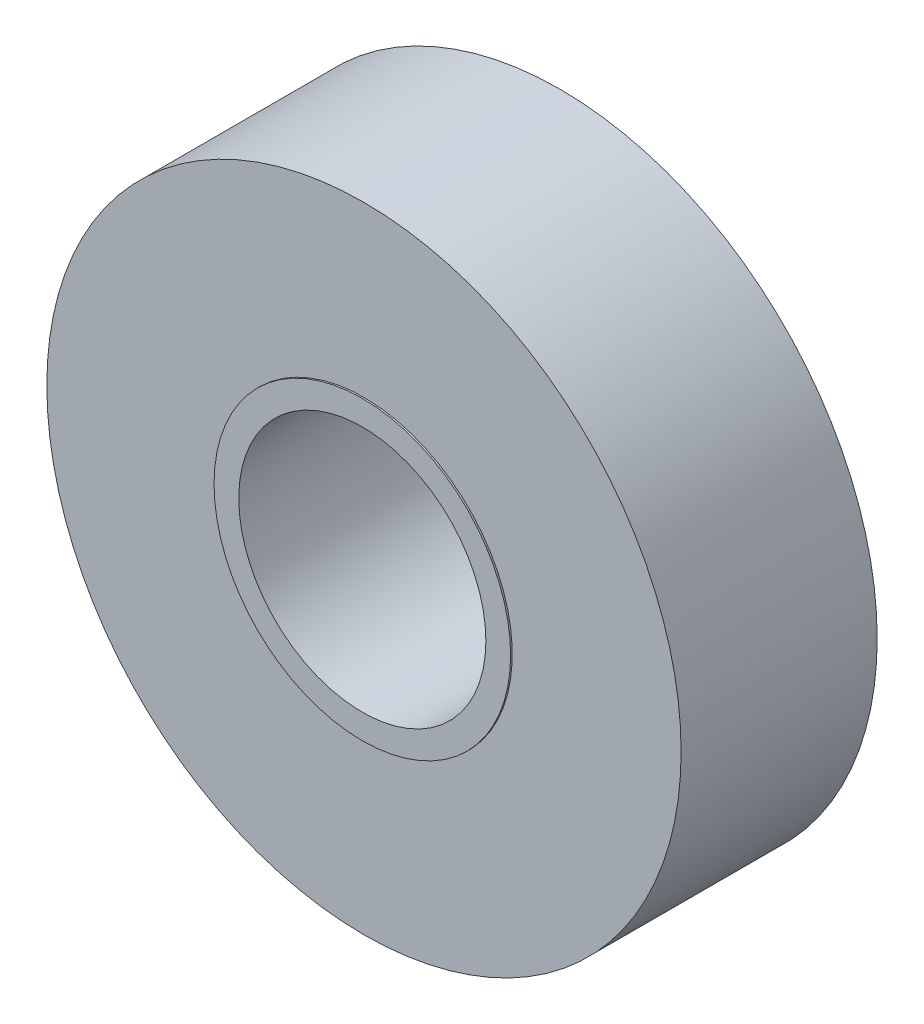
SolidWorks part; units mm, degrees
ref_plane "Alzado" through (0, 0, 0) normal (0, 0, 1) x (1, 0, 0)
ref_plane "Planta" through (0, 0, 0) normal (0, 1, 0) x (1, 0, 0)
ref_plane "Vista lateral" through (0, 0, 0) normal (1, 0, 0) x (0, 0, -1)
sketch "Croquis1" plane through (0, 0, 0) normal (0, 0, 1) x (1, 0, 0)
  circle A0 centre (0, 0) radius 7.5
  circle A1 centre (0, 0) radius 9
  circle A3 centre (0, 0) radius 9
  circle A4 centre (0, 0) radius 1.5
  circle A5 centre (0, 0) radius 7.4545
  circle A6 centre (0, 0) radius 7.5
  dimension "D1" = 15
  dimension "D2" = 18
  dimension "D3" = 3
extrude "Saliente-Extruir1" add sketch "Croquis1" along normal blind 12 contours A1 A0 region at (-8.7454, 0, 0)
sketch "Croquis2" plane through (0, 0, 0) normal (0, 0, 1) x (1, 0, 0)
  circle A0 centre (0, 0) radius 7.5
extrude "Saliente-Extruir2" add sketch "Croquis2" along normal blind 1 and the other way blind 0.1
sketch "Croquis3" plane through (0, 0, 0) normal (0, 0, 1) x (1, 0, 0)
  circle A0 centre (0, 0) radius 5.2
  circle A1 centre (0, 0) radius 1.5
  dimension "D1" = 10.4
  dimension "D2" = 3
extrude "Saliente-Extruir4" add sketch "Croquis3" against normal blind 3 contours A0 | A1
sketch "Croquis4" plane through (0, 0, 0) normal (0, 0, -1) x (-1, 0, 0)
  circle A0 centre (0, 0) radius 9
  circle A1 centre (0, 0) radius 19.25
  dimension "D1" = 38.5
extrude "Saliente-Extruir5" add sketch "Croquis4" against normal blind 11.9
sketch "Croquis6" plane through (0, 0, -3) normal (0, 0, -1) x (-1, 0, 0)
  circle A0 centre (0, 0) radius 1.5
extrude "Cortar-Extruir1" [suppressed] cut sketch "Croquis6" against normal blind 10
